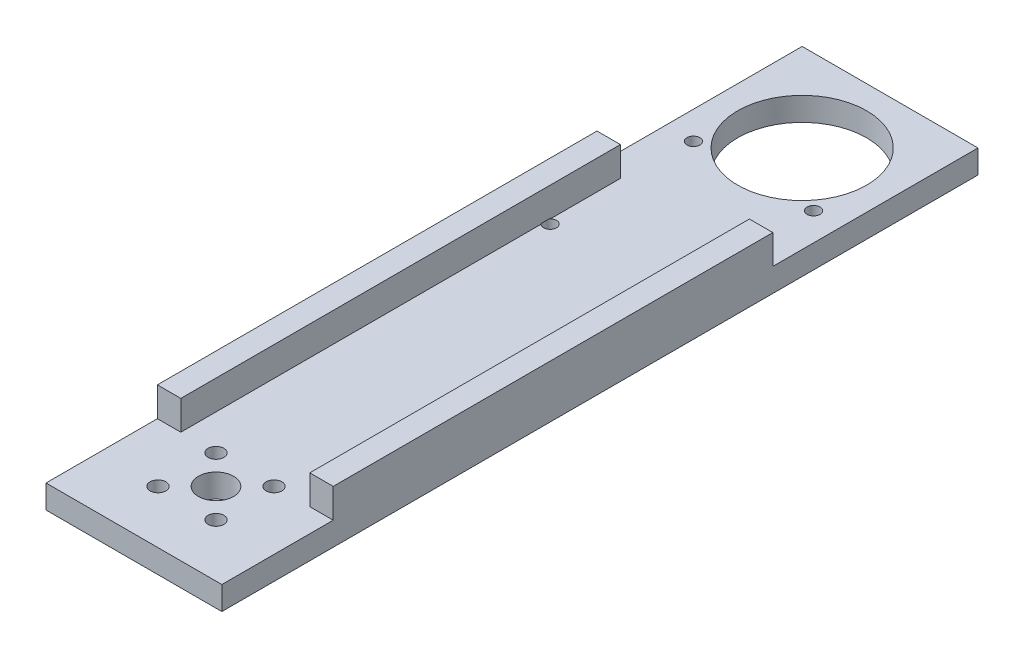
SolidWorks part; units mm, degrees
ref_plane "Front Plane" through (0, 0, 0) normal (0, 0, 1) x (1, 0, 0)
ref_plane "Top Plane" through (0, 0, 0) normal (0, 1, 0) x (1, 0, 0)
ref_plane "Right Plane" through (0, 0, 0) normal (1, 0, 0) x (0, 0, -1)
ref_plane "PZ_m115_000" through (0, 0, -115) normal (0, 0, 1) x (1, 0, 0)
sketch "S_box1" plane through (0, 0, -115) normal (0, 0, 1) x (1, 0, 0)
  line L0 (-15, 18.625) -> (15, 18.625)
  line L1 (15, 18.625) -> (15, 22.625)
  line L2 (15, 22.625) -> (-15, 22.625)
  line L3 (-15, 22.625) -> (-15, 18.625)
  dimension "P1" = 15
  dimension "P2" = 18.625
  dimension "P3" = 15
  dimension "P4" = 18.625
  dimension "P5" = 15
  dimension "P6" = 22.625
  dimension "P7" = 15
  dimension "P8" = 22.625
extrude "Boss_1" add sketch "S_box1" along normal blind 129
ref_plane "PZ_m80_000" through (0, 0, -80) normal (0, 0, 1) x (1, 0, 0)
sketch "S_box2" plane through (0, 0, -80) normal (0, 0, 1) x (1, 0, 0)
  line L0 (-15, 22.125) -> (-11, 22.125)
  line L1 (-11, 22.125) -> (-11, 27.625)
  line L2 (-11, 27.625) -> (-15, 27.625)
  line L3 (-15, 27.625) -> (-15, 22.125)
  dimension "P1" = 15
  dimension "P2" = 22.125
  dimension "P3" = 11
  dimension "P4" = 22.125
  dimension "P5" = 11
  dimension "P6" = 27.625
  dimension "P7" = 15
  dimension "P8" = 27.625
extrude "Boss_2" add sketch "S_box2" along normal blind 75
sketch "S_box3" plane through (0, 0, -80) normal (0, 0, 1) x (1, 0, 0)
  line L0 (11, 22.125) -> (15, 22.125)
  line L1 (15, 22.125) -> (15, 27.625)
  line L2 (15, 27.625) -> (11, 27.625)
  line L3 (11, 27.625) -> (11, 22.125)
  dimension "P1" = 11
  dimension "P2" = 22.125
  dimension "P3" = 15
  dimension "P4" = 22.125
  dimension "P5" = 15
  dimension "P6" = 27.625
  dimension "P7" = 11
  dimension "P8" = 27.625
extrude "Boss_3" add sketch "S_box3" along normal blind 75
ref_plane "PY_p18_525" through (0, 18.525, 0) normal (0, 1, 0) x (1, 0, 0)
sketch "S_hole4" plane through (0, 18.525, 0) normal (0, 1, 0) x (1, 0, 0)
  circle A0 centre (0, 0) radius 3
  dimension "D1_S_hole4" = 6
extrude "Hole_4" cut sketch "S_hole4" along normal blind 4.2
sketch "S_hole5" plane through (0, 18.525, 0) normal (0, 1, 0) x (1, 0, 0)
  circle A0 centre (4.9497, -4.9497) radius 1.35
  dimension "D1_S_hole5" = 2.7
  dimension "P2" = 4.9497
  dimension "P3" = 4.9497
extrude "Hole_5" cut sketch "S_hole5" along normal blind 4.2
sketch "S_hole6" plane through (0, 18.525, 0) normal (0, 1, 0) x (1, 0, 0)
  circle A0 centre (-4.9497, -4.9497) radius 1.35
  dimension "D1_S_hole6" = 2.7
  dimension "P2" = 4.9497
  dimension "P3" = 4.9497
extrude "Hole_6" cut sketch "S_hole6" along normal blind 4.2
sketch "S_hole7" plane through (0, 18.525, 0) normal (0, 1, 0) x (1, 0, 0)
  circle A0 centre (-4.9497, 4.9497) radius 1.35
  dimension "D1_S_hole7" = 2.7
  dimension "P2" = 4.9497
  dimension "P3" = 4.9497
extrude "Hole_7" cut sketch "S_hole7" along normal blind 4.2
sketch "S_hole8" plane through (0, 18.525, 0) normal (0, 1, 0) x (1, 0, 0)
  circle A0 centre (4.9497, 4.9497) radius 1.35
  dimension "D1_S_hole8" = 2.7
  dimension "P2" = 4.9497
  dimension "P3" = 4.9497
extrude "Hole_8" cut sketch "S_hole8" along normal blind 4.2
sketch "S_hole9" plane through (0, 18.525, 0) normal (0, 1, 0) x (1, 0, 0)
  circle A0 centre (0, 100) radius 11
  dimension "D1_S_hole9" = 22
  dimension "P2" = 100
extrude "Hole_9" cut sketch "S_hole9" along normal blind 4.2
sketch "S_hole10" plane through (0, 18.525, 0) normal (0, 1, 0) x (1, 0, 0)
  circle A0 centre (-10.25, 91.7) radius 1.1
  dimension "D1_S_hole10" = 2.2
  dimension "P2" = 10.25
  dimension "P3" = 91.7
extrude "Hole_10" cut sketch "S_hole10" along normal blind 4.2
sketch "S_hole11" plane through (0, 18.525, 0) normal (0, 1, 0) x (1, 0, 0)
  circle A0 centre (10.25, 91.7) radius 1.1
  dimension "D1_S_hole11" = 2.2
  dimension "P2" = 10.25
  dimension "P3" = 91.7
extrude "Hole_11" cut sketch "S_hole11" along normal blind 4.2
sketch "S_hole12" plane through (0, 18.525, 0) normal (0, 1, 0) x (1, 0, 0)
  circle A0 centre (-10.25, 67.25) radius 1.1
  dimension "D1_S_hole12" = 2.2
  dimension "P2" = 10.25
  dimension "P3" = 67.25
extrude "Hole_12" cut sketch "S_hole12" along normal blind 4.2
sketch "S_hole13" plane through (0, 18.525, 0) normal (0, 1, 0) x (1, 0, 0)
  circle A0 centre (10.25, 67.25) radius 1.1
  dimension "D1_S_hole13" = 2.2
  dimension "P2" = 10.25
  dimension "P3" = 67.25
extrude "Hole_13" cut sketch "S_hole13" along normal blind 4.2
equation "\"plate_t\" = 3"
equation "\"clearance\" = 0.4"
